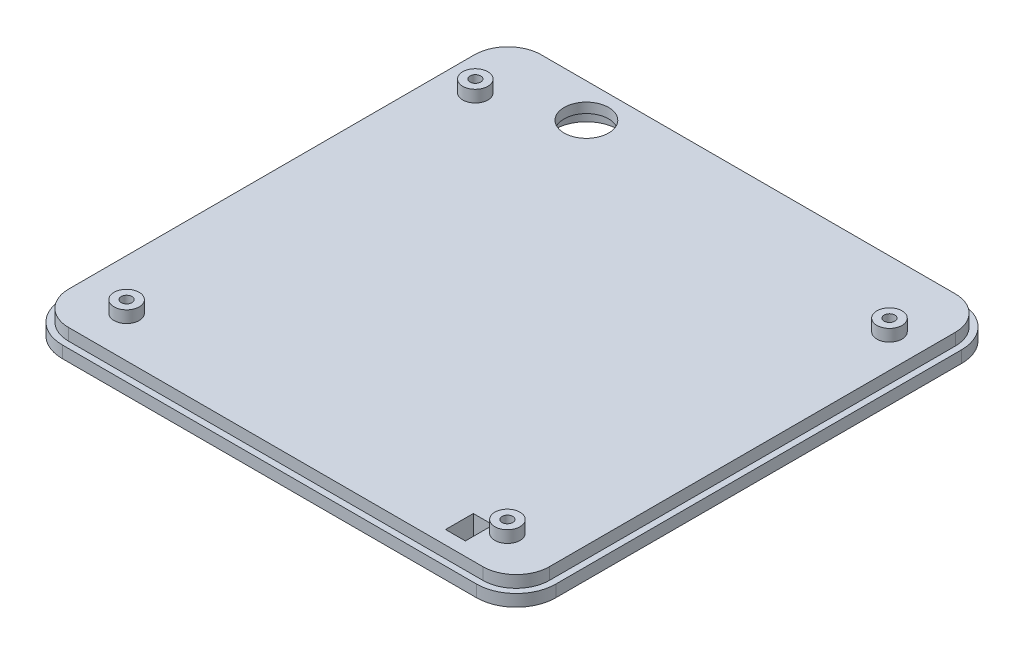
SolidWorks part; units mm, degrees
ref_plane "Front Plane" through (0, 0, 0) normal (0, 0, 1) x (1, 0, 0)
ref_plane "Top Plane" through (0, 0, 0) normal (0, 1, 0) x (1, 0, 0)
ref_plane "Right Plane" through (0, 0, 0) normal (1, 0, 0) x (0, 0, -1)
sketch "Sketch1" plane through (0, 0, 0) normal (0, 1, 0) x (1, 0, 0)
  line L0 (-52.2, 47.9825) -> (48, -44.1218) construction
  line L1 (-48, -44.1218) -> (52.2, 47.9825) construction
  line L2 (-52.2, 47.9825) -> (-48, -44.1218) construction
  line L3 (-48, -44.1218) -> (48, -44.1218) construction
  line L4 (48, -44.1218) -> (52.2, 47.9825) construction
  line L5 (52.2, 47.9825) -> (-52.2, 47.9825) construction
  line L7 (-52.2, 66.1825) -> (52.2, 66.1825)
  line L8 (-62.2, 56.1825) -> (-62.2, -46.1218)
  line L9 (-52.2, -56.1218) -> (52.2, -56.1218)
  line L10 (62.2, 56.1825) -> (62.2, -46.1218)
  circle A0 centre (-48, -44.1218) radius 1.35
  circle A1 centre (-52.2, 47.9825) radius 1.35
  circle A2 centre (52.2, 47.9825) radius 1.35
  circle A3 centre (48, -44.1218) radius 1.35
  arc A4 (-62.2, -46.1218) -> (-52.2, -56.1218) centre (-52.2, -46.1218) ccw
  arc A5 (52.2, -56.1218) -> (62.2, -46.1218) centre (52.2, -46.1218) ccw
  arc A6 (52.2, 66.1825) -> (62.2, 56.1825) centre (52.2, 56.1825) cw
  arc A7 (-52.2, 66.1825) -> (-62.2, 56.1825) centre (-52.2, 56.1825) ccw
  point P4 (0, 0)
  point P6 (9.2278, -42.5901)
  point P22 (-43.5025, -45.82)
  circle B0 centre (-52.2, 47.9825) radius 1.25 construction
  circle B1 centre (-48, -44.1218) radius 1.25 construction
  circle B2 centre (48, -44.1218) radius 1.25 construction
  circle B3 centre (52.2, 47.9825) radius 1.25 construction
  dimension "D8" = 2.7
  dimension "D9" = 10
  dimension "D10" = 10
  dimension "D11" = 10
  dimension "D12" = 10
  dimension "D1" = 104.4
  dimension "D2" = 96
  dimension "D3" = 12
  dimension "D4" = 10
  dimension "D5" = 18.2
  dimension "D6" = 10
  dimension "D7" = 92.1043
sketch_block_instance "Main Board-1"
sketch_block "Main Board" parameters "D1"=2.5, "D2"=104.4, "D3"=96, "D4"=92.2
extrude "Boss-Extrude1" add sketch "Sketch1" along normal blind 6 contours L7 A7 L8 A4 L9 A5 L10 A6 A0 A1 A2 A3 region at (0, 0, -5.035)
sketch "Sketch2" plane through (0, 0, 0) normal (0, -1, 0) x (1, 0, 0)
  line L4 (-52.2, -66.1825) -> (52.2, -66.1825)
  line L5 (62.2, -56.1825) -> (62.2, 46.1218)
  line L6 (52.2, 56.1218) -> (-52.2, 56.1218)
  line L7 (-62.2, 46.1218) -> (-62.2, -56.1825)
  line L8 (-52.2, -66.1825) -> (52.2, -66.1825)
  line L9 (62.2, -56.1825) -> (62.2, 46.1218)
  line L10 (52.2, 56.1218) -> (-52.2, 56.1218)
  line L11 (-62.2, 46.1218) -> (-62.2, -56.1825)
  circle A0 centre (-52.2, -47.9825) radius 1.35 construction
  circle A1 centre (52.2, -47.9825) radius 1.35 construction
  circle A2 centre (48, 44.1218) radius 1.35 construction
  circle A3 centre (-48, 44.1218) radius 1.35 construction
  arc A4 (52.2, -66.1825) -> (62.2, -56.1825) centre (52.2, -56.1825) ccw
  arc A5 (62.2, 46.1218) -> (52.2, 56.1218) centre (52.2, 46.1218) ccw
  arc A6 (-52.2, 56.1218) -> (-62.2, 46.1218) centre (-52.2, 46.1218) ccw
  arc A7 (-62.2, -56.1825) -> (-52.2, -66.1825) centre (-52.2, -56.1825) ccw
  arc A8 (52.2, -66.1825) -> (62.2, -56.1825) centre (52.2, -56.1825) ccw
  arc A9 (62.2, 46.1218) -> (52.2, 56.1218) centre (52.2, 46.1218) ccw
  arc A10 (-52.2, 56.1218) -> (-62.2, 46.1218) centre (-52.2, 46.1218) ccw
  arc A11 (-62.2, -56.1825) -> (-52.2, -66.1825) centre (-52.2, -56.1825) ccw
  circle A12 centre (-52.2, -47.9825) radius 1.35
  circle A13 centre (52.2, -47.9825) radius 1.35
  circle A14 centre (48, 44.1218) radius 1.35
  circle A15 centre (-48, 44.1218) radius 1.35
  circle A16 centre (-48, 44.1218) radius 2.5
  circle A17 centre (48, 44.1218) radius 2.5
  circle A18 centre (52.2, -47.9825) radius 2.5
  circle A19 centre (-52.2, -47.9825) radius 2.5
  circle M9 centre (-48, 44.1218) radius 1.35
  circle M10 centre (-52.2, -47.9825) radius 1.35
  circle M11 centre (52.2, -47.9825) radius 1.35
  circle M12 centre (48, 44.1218) radius 1.35
  dimension "D2" = 5
  dimension "D1" = 0
extrude "Cut-Extrude1" cut sketch "Sketch2" against normal blind 3 contours A16 M9 | A19 M10 | A18 M11 | A17 M12 region at (-50.4293, 0, 44.1218) region at (45.5707, 0, 44.1218) region at (49.7707, 0, -47.9825) region at (-54.6293, 0, -47.9825)
sketch "Sketch3" plane through (0, 6, 0) normal (0, 1, 0) x (1, 0, 0)
  circle A0 centre (-48, -44.1218) radius 1.35 construction
  circle A1 centre (48, -44.1218) radius 1.35 construction
  circle A2 centre (52.2, 47.9825) radius 1.35 construction
  circle A3 centre (-52.2, 47.9825) radius 1.35 construction
  circle A4 centre (-48, -44.1218) radius 1.35
  circle A5 centre (48, -44.1218) radius 1.35
  circle A6 centre (52.2, 47.9825) radius 1.35
  circle A7 centre (-52.2, 47.9825) radius 1.35
  circle A8 centre (-52.2, 47.9825) radius 3.175
  circle A9 centre (52.2, 47.9825) radius 3.175
  circle A10 centre (48, -44.1218) radius 3.175
  circle A11 centre (-48, -44.1218) radius 3.175
  circle M1 centre (-48, -44.1218) radius 1.35
  circle M2 centre (-52.2, 47.9825) radius 1.35
  circle M3 centre (52.2, 47.9825) radius 1.35
  circle M4 centre (48, -44.1218) radius 1.35
  dimension "D1" = 6.35
extrude "Boss-Extrude2" add sketch "Sketch3" along normal blind 3 contours A8 M2 | A9 M3 | A10 M4 | A11 M1 region at (-55.2852, 6, -47.9825) region at (49.1148, 6, -47.9825) region at (44.9148, 6, 44.1218) region at (-51.0852, 6, 44.1218)
sketch "Sketch4" plane through (0, 6, 0) normal (0, 1, 0) x (1, 0, 0)
  line L0 (-60.6, 56.1825) -> (-60.6, -46.1218)
  line L1 (-52.2, -54.5218) -> (52.2, -54.5218)
  line L2 (60.6, -46.1218) -> (60.6, 56.1825)
  line L3 (52.2, 64.5825) -> (-52.2, 64.5825)
  line L4 (52.2, 66.1825) -> (-52.2, 66.1825)
  line L5 (-62.2, 56.1825) -> (-62.2, -46.1218)
  line L6 (-52.2, -56.1218) -> (52.2, -56.1218)
  line L7 (62.2, -46.1218) -> (62.2, 56.1825)
  line L8 (52.2, 66.1825) -> (-52.2, 66.1825)
  line L9 (-62.2, 56.1825) -> (-62.2, -46.1218)
  line L10 (-52.2, -56.1218) -> (52.2, -56.1218)
  line L11 (62.2, -46.1218) -> (62.2, 56.1825)
  arc A0 (-52.2, 64.5825) -> (-60.6, 56.1825) centre (-52.2, 56.1825) ccw
  arc A1 (-60.6, -46.1218) -> (-52.2, -54.5218) centre (-52.2, -46.1218) ccw
  arc A2 (52.2, -54.5218) -> (60.6, -46.1218) centre (52.2, -46.1218) ccw
  arc A3 (60.6, 56.1825) -> (52.2, 64.5825) centre (52.2, 56.1825) ccw
  arc A4 (-52.2, 66.1825) -> (-62.2, 56.1825) centre (-52.2, 56.1825) ccw
  arc A5 (-62.2, -46.1218) -> (-52.2, -56.1218) centre (-52.2, -46.1218) ccw
  arc A6 (52.2, -56.1218) -> (62.2, -46.1218) centre (52.2, -46.1218) ccw
  arc A7 (62.2, 56.1825) -> (52.2, 66.1825) centre (52.2, 56.1825) ccw
  arc A8 (-52.2, 66.1825) -> (-62.2, 56.1825) centre (-52.2, 56.1825) ccw
  arc A9 (-62.2, -46.1218) -> (-52.2, -56.1218) centre (-52.2, -46.1218) ccw
  arc A10 (52.2, -56.1218) -> (62.2, -46.1218) centre (52.2, -46.1218) ccw
  arc A11 (62.2, 56.1825) -> (52.2, 66.1825) centre (52.2, 56.1825) ccw
  dimension "D1" = 0
  dimension "D2" = 1.6
extrude "Cut-Extrude2" cut sketch "Sketch4" against normal blind 3
sketch "Sketch5" plane through (0, 6, 0) normal (0, 1, 0) x (1, 0, 0)
  circle A0 centre (-35.1, 52.7125) radius 1.35
  circle A1 centre (50.09, 37.7525) radius 1.35
  dimension "D1" = 4.73
  dimension "D3" = 2.7
  dimension "D2" = 17.1
  dimension "D4" = 10.23
  dimension "D5" = 2.11
sketch "Sketch7" plane through (0, 6, 0) normal (0, 1, 0) x (1, 0, 0)
  circle A0 centre (-32.2, 55.9825) radius 5.6
  dimension "D1" = 11.2
  dimension "D2" = 8
  dimension "D3" = 20
extrude "Cut-Extrude3" cut sketch "Sketch7" against normal blind 10
sketch "Sketch8" plane through (0, 0, 0) normal (0, -1, 0) x (1, 0, 0)
  circle A0 centre (-32.2, -55.9825) radius 5.6 construction
  circle A1 centre (-32.2, -55.9825) radius 5.6
  circle A2 centre (-32.2, -55.9825) radius 8
  dimension "D1" = 16
extrude "Cut-Extrude4" cut sketch "Sketch8" against normal blind 3.5
sketch "Sketch9" plane through (0, 0, 0) normal (0, -1, 0) x (1, 0, 0)
  line L1 (44.4, 44.1218) -> (39.4, 44.1218)
  line L2 (44.4, 44.1218) -> (44.4, 51.1218)
  line L3 (44.4, 51.1218) -> (39.4, 51.1218)
  line L4 (39.4, 44.1218) -> (39.4, 51.1218)
  point P4 (41.9, 51.1218)
  point P5 (44.4, 47.6218)
  dimension "D1" = 7
  dimension "D2" = 5
  dimension "D3" = 6.1
  dimension "D4" = 3.5
extrude "Cut-Extrude5" cut sketch "Sketch9" against normal through all
